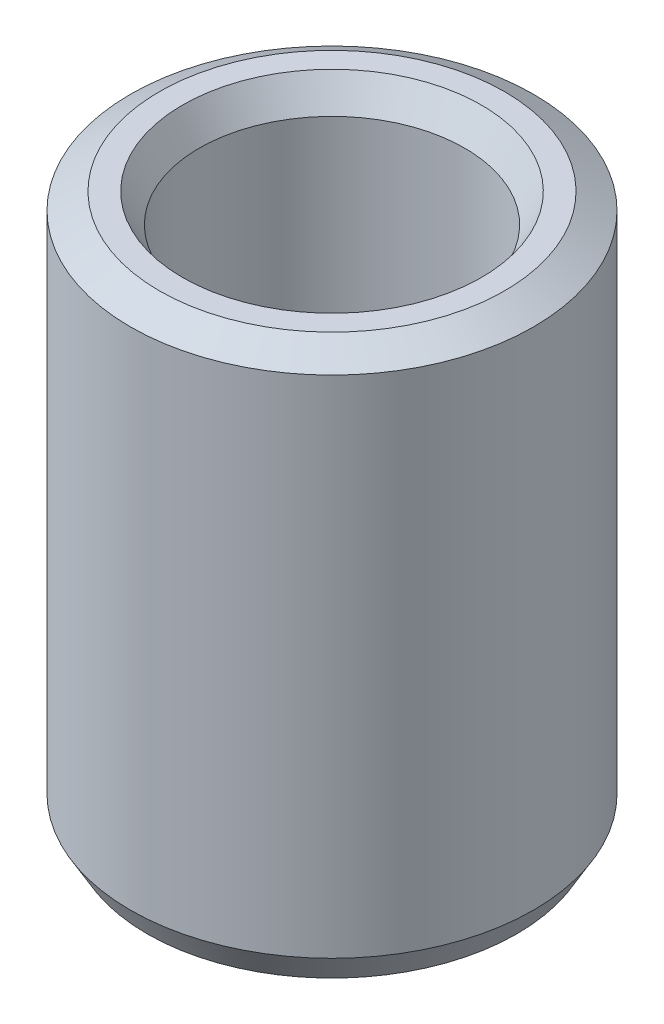
SolidWorks part; units mm, degrees
ref_plane "Front Plane" through (0, 0, 0) normal (0, 0, 1) x (1, 0, 0)
ref_plane "Top Plane" through (0, 0, 0) normal (0, 1, 0) x (1, 0, 0)
ref_plane "Right Plane" through (0, 0, 0) normal (1, 0, 0) x (0, 0, -1)
sketch "Sketch1" plane through (0, 0, 0) normal (0, 1, 0) x (1, 0, 0)
  circle A0 centre (0, 0) radius 32.5
  dimension "SLEEVE_OD" = 65
extrude "Boss-Extrude1" add sketch "Sketch1" along normal blind 88.8156
sketch "Sketch2" plane through (0, 0, 0) normal (0, 1, 0) x (1, 0, 0)
  circle A0 centre (0, 0) radius 21.4003
  dimension "BORE_D" = 42.8005
extrude "Cut-Extrude1" cut sketch "Sketch2" along normal through all
chamfer "Chamfer1" distance 2.6962 angle 60 4 edges at (0, 88.8156, 21.4003) (0, 0, 21.4003) (0, 0, 32.5) (0, 88.8156, 32.5) first distance on face at (0, 88.8156, 21.4003) first distance on face at (0, 0, 21.4003) first distance on face at (0, 88.8156, 32.5)
